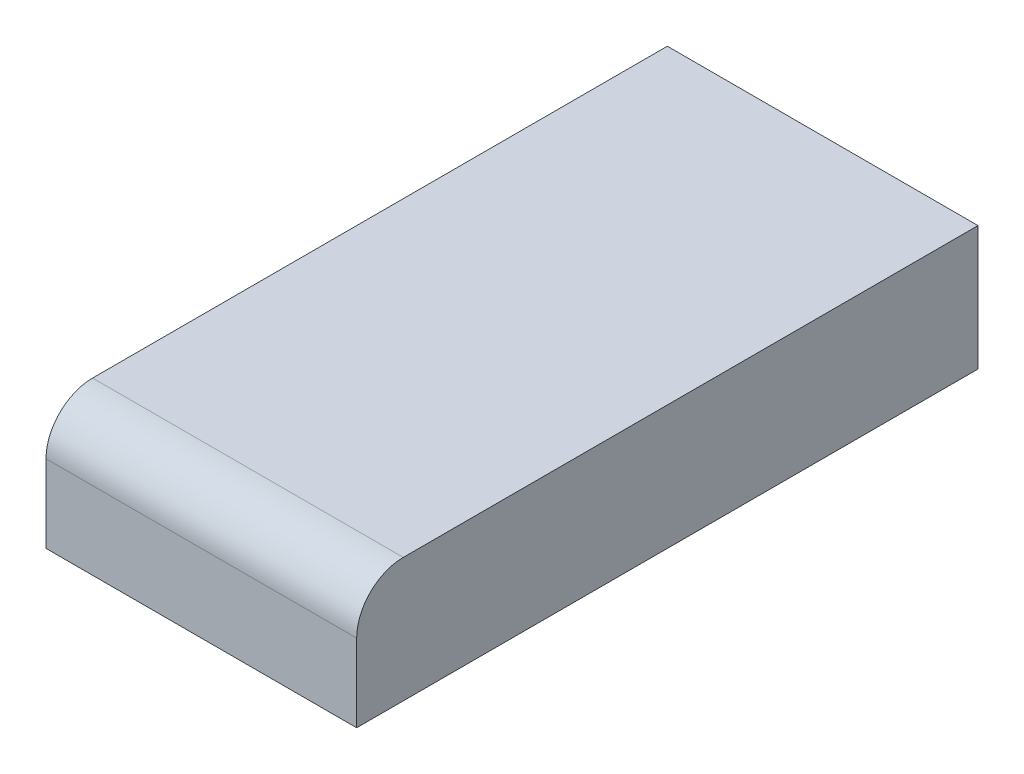
SolidWorks part; units mm, degrees
ref_plane "Front Plane" through (0, 0, 0) normal (0, 0, 1) x (1, 0, 0)
ref_plane "Top Plane" through (0, 0, 0) normal (0, 1, 0) x (1, 0, 0)
ref_plane "Right Plane" through (0, 0, 0) normal (1, 0, 0) x (0, 0, -1)
sketch "Sketch2" plane through (0, 33.7573, 0) normal (0, 1, 0) x (1, 0, 0)
  line L1 (-80, 10.5) -> (-100, 10.5)
  line L2 (-80, 10.5) -> (-80, 50.5)
  line L3 (-80, 50.5) -> (-100, 50.5)
  line L4 (-100, 10.5) -> (-100, 50.5)
extrude "Boss-Extrude2" add sketch "Sketch2" along normal blind 8
fillet "Fillet2" radius 3 1 edges at (-90, 41.7573, -10.5)
